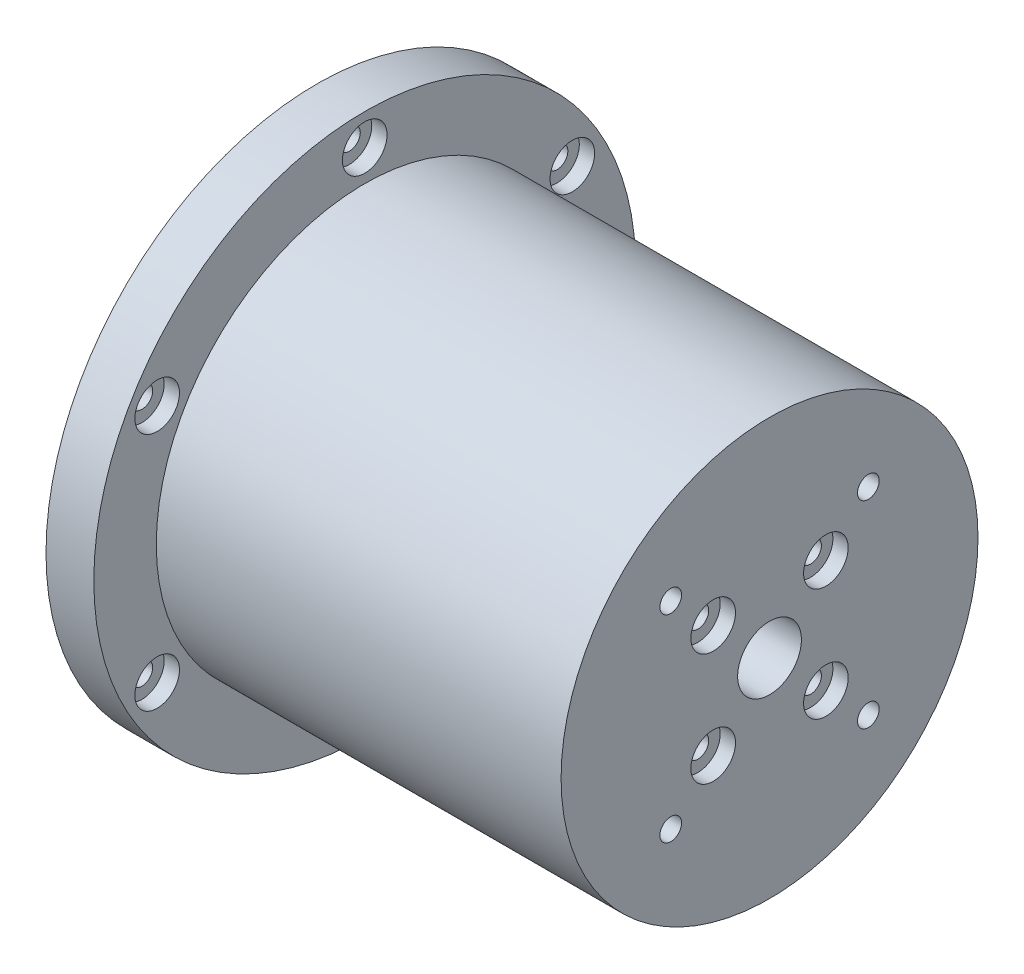
SolidWorks part; units mm, degrees
material "7075-O (SS)"
ref_plane "Front" through (0, 0, 0) normal (0, 0, 1) x (1, 0, 0)
ref_plane "Top" through (0, 0, 0) normal (0, 1, 0) x (1, 0, 0)
ref_plane "Right" through (0, 0, 0) normal (1, 0, 0) x (0, 0, -1)
sketch "Croquis1" plane through (0, 0, 0) normal (1, 0, 0) x (0, 0, -1)
  circle A0 centre (0, 0) radius 32.7
  circle A1 centre (0, 0) radius 5
  dimension "D1" = 65.4
  dimension "D2" = 10
extrude "Saliente-Extruir1" add sketch "Croquis1" along normal mid plane 8.5
hole_wizard "Refrentado para tornillo con cabeza troncocónica de M31" positions "Croquis2" profile "Croquis4" counterbore size "M3" standard "Ansi Metric" end condition up to next
sketch "Croquis2" plane through (4.25, 0, 0) normal (1, 0, 0) x (0, 0, -1)
  line L1 (-8.8388, -8.8388) -> (8.8388, -8.8388) construction
  line L2 (-8.8388, -8.8388) -> (-8.8388, 8.8388) construction
  line L3 (-8.8388, 8.8388) -> (8.8388, 8.8388) construction
  line L4 (8.8388, -8.8388) -> (8.8388, 8.8388) construction
  line L5 (-8.8388, -8.8388) -> (8.8388, 8.8388) construction
  line L6 (-8.8388, 8.8388) -> (8.8388, -8.8388) construction
  point P2 (8.8388, 8.8388)
  point P25 (-8.8388, -8.8388)
  point P26 (-8.8388, 8.8388)
  point P27 (8.8388, -8.8388)
  dimension "D1" = 25
sketch "Croquis4" plane through (4.25, 8.8388, -8.8388) normal (0, 1, 0) x (0, 0, -1)
  line L0 (0, 0) -> (0, 8.5)
  line L1 (0, 8.5) -> (1.7, 8.5)
  line L3 (1.7, 8.5) -> (1.7, 2.4)
  line L4 (1.7, 2.4) -> (3.5, 2.4)
  line L5 (3.5, 2.4) -> (3.5, 0)
  line L7 (3.5, 0) -> (0, 0)
  line L11 (0, -6.35) -> (0, 107.95) construction
  dimension "Diámetro de taladro hasta el siguiente" = 3.4
  dimension "Profundidad de taladro hasta el siguiente" = 8.5
  dimension "Diámetro de refrentado" = 7
  dimension "Profundidad de refrentado" = 2.4
sketch "Croquis5" plane through (-4.25, 0, 0) normal (-1, 0, 0) x (0, 0, 1)
  circle A0 centre (0, 0) radius 21.5
  circle A1 centre (0, 0) radius 32.7 construction
  circle A2 centre (0, 0) radius 32.7
  dimension "D1" = 43
extrude "Saliente-Extruir2" add sketch "Croquis5" along normal blind 55
hole_wizard "Taladro de margen para M31" positions "Croquis6" profile "Croquis8" hole size "M3" standard "Ansi Metric"
sketch "Croquis6" plane through (-59.25, 0, 0) normal (-1, 0, 0) x (0, 0, 1)
  line L1 (-17.075, -17.075) -> (17.075, -17.075) construction
  line L2 (-17.075, -17.075) -> (-17.075, 17.075) construction
  line L3 (-17.075, 17.075) -> (17.075, 17.075) construction
  line L4 (17.075, -17.075) -> (17.075, 17.075) construction
  line L5 (-17.075, -17.075) -> (17.075, 17.075) construction
  line L6 (-17.075, 17.075) -> (17.075, -17.075) construction
  point P2 (17.075, 17.075)
  point P25 (-17.075, -17.075)
  point P26 (-17.075, 17.075)
  point P27 (17.075, -17.075)
  dimension "D1" = 34.15
sketch "Croquis8" plane through (-59.25, 17.075, 17.075) normal (0, 1, 0) x (0, 0, 1)
  line L0 (0, 0) -> (0, 16.0215)
  line L1 (0, 16.0215) -> (1.7, 15)
  line L2 (1.7, 15) -> (1.7, 0)
  line L5 (1.7, 0) -> (0, 0)
  line L10 (0, 16.0215) -> (-1.7, 15) construction
  line L11 (0, -6.35) -> (0, 107.95) construction
  dimension "Diámetro de taladro" = 3.4
  dimension "Profundidad de taladro" = 15
  dimension "Ángulo de perforador" = 118
hole_wizard "Taladro de margen para M32" positions "Croquis9" profile "Croquis10" hole size "M3" standard "Ansi Metric"
sketch "Croquis9" plane through (4.25, 0, 0) normal (1, 0, 0) x (0, 0, -1)
  line L1 (-15.5, -15.5) -> (15.5, -15.5) construction
  line L2 (-15.5, -15.5) -> (-15.5, 15.5) construction
  line L3 (-15.5, 15.5) -> (15.5, 15.5) construction
  line L4 (15.5, -15.5) -> (15.5, 15.5) construction
  line L5 (-15.5, -15.5) -> (15.5, 15.5) construction
  line L6 (-15.5, 15.5) -> (15.5, -15.5) construction
  point P2 (15.5, 15.5)
  point P13 (-15.5, -15.5)
  point P14 (-15.5, 15.5)
  point P15 (15.5, -15.5)
  dimension "D1" = 31
sketch "Croquis10" plane through (4.25, 15.5, -15.5) normal (0, 1, 0) x (0, 0, -1)
  line L0 (0, 0) -> (0, 17.5215)
  line L1 (0, 17.5215) -> (1.7, 16.5)
  line L2 (1.7, 16.5) -> (1.7, 0)
  line L5 (1.7, 0) -> (0, 0)
  line L10 (0, 17.5215) -> (-1.7, 16.5) construction
  line L11 (0, -6.35) -> (0, 107.95) construction
  dimension "Diámetro de taladro" = 3.4
  dimension "Profundidad de taladro" = 16.5
  dimension "Ángulo de perforador" = 118
sketch "Croquis16" plane through (-59.25, 0, 0) normal (-1, 0, 0) x (0, 0, 1)
  line L6 (-18.5, -21.5) -> (18.5, -21.5)
  line L14 (-21.5, -18.5) -> (-21.5, 18.5)
  line L15 (-18.5, 21.5) -> (18.5, 21.5)
  line L16 (21.5, -18.5) -> (21.5, 18.5)
  line L17 (-21.5, -21.5) -> (21.5, 21.5) construction
  line L18 (-21.5, 21.5) -> (21.5, -21.5) construction
  circle A1 centre (0, 0) radius 42.5
  circle A3 centre (0, 0) radius 21.5 construction
  arc A4 (-18.5, -21.5) -> (-21.5, -18.5) centre (-18.5, -18.5) cw
  arc A5 (18.5, -21.5) -> (21.5, -18.5) centre (18.5, -18.5) ccw
  arc A6 (18.5, 21.5) -> (21.5, 18.5) centre (18.5, 18.5) cw
  arc A7 (-21.5, 18.5) -> (-18.5, 21.5) centre (-18.5, 18.5) cw
  dimension "D1" = 85
  dimension "D2" = 3
extrude "Saliente-Extruir3" add sketch "Croquis16" along normal blind 7.5
hole_wizard "Refrentado para tornillo con cabeza troncocónica de M32" positions "Croquis20" profile "Croquis21" counterbore size "M3" standard "Ansi Metric" end condition up to next
sketch "Croquis20" plane through (-59.25, 0, 0) normal (1, 0, 0) x (0, 0, -1)
  line L0 (0, 42.5) -> (0, 32.7) construction
  line L1 (0, 34.925) -> (0, -34.925) construction
  circle A0 centre (0, 0) radius 42.5 construction
  circle A1 centre (0, 0) radius 32.7 construction
  point P14 (0, 37.6)
  point P21 (32.5626, 18.8)
  point P22 (32.5626, -18.8)
  point P23 (0, -37.6)
  point P24 (-32.5626, -18.8)
  point P25 (-32.5626, 18.8)
  dimension "D1" = 6
sketch "Croquis21" plane through (-59.25, 18.8, 32.5626) normal (0, 1, 0) x (0, 0, -1)
  line L0 (0, 0) -> (0, 7.5)
  line L1 (0, 7.5) -> (1.7, 7.5)
  line L3 (1.7, 7.5) -> (1.7, 2.4)
  line L4 (1.7, 2.4) -> (3.5, 2.4)
  line L5 (3.5, 2.4) -> (3.5, 0)
  line L7 (3.5, 0) -> (0, 0)
  line L11 (0, -6.35) -> (0, 107.95) construction
  dimension "Diámetro de taladro hasta el siguiente" = 3.4
  dimension "Profundidad de taladro hasta el siguiente" = 7.5
  dimension "Diámetro de refrentado" = 7
  dimension "Profundidad de refrentado" = 2.4
